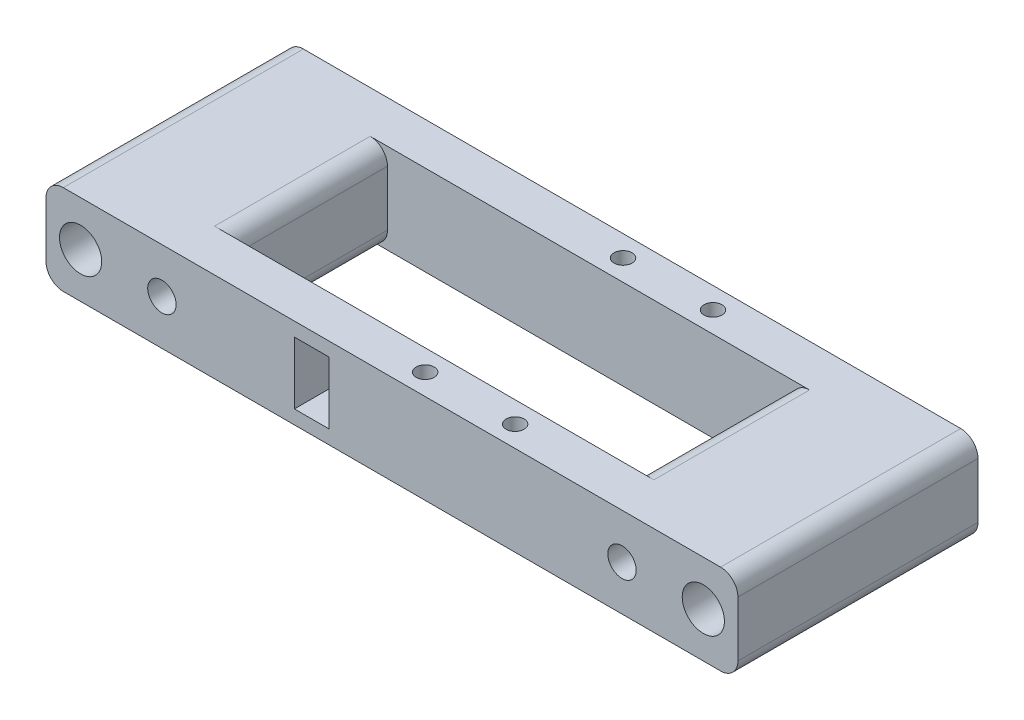
SolidWorks part; units mm, degrees
ref_plane "Front Plane" through (0, 0, 0) normal (0, 0, 1) x (1, 0, 0)
ref_plane "Top Plane" through (0, 0, 0) normal (0, 1, 0) x (1, 0, 0)
ref_plane "Right Plane" through (0, 0, 0) normal (1, 0, 0) x (0, 0, -1)
sketch "Sketch1" plane through (0, 0, 0) normal (0, 0, 1) x (1, 0, 0)
  line L0 (-58.5, 26) -> (-58.5, 0) construction
  line L1 (0, 0) -> (-100, 0)
  line L2 (0, 0) -> (0, 26)
  line L3 (0, 26) -> (-100, 26)
  line L4 (-100, 0) -> (-100, 26)
  circle A0 centre (-90, 13) radius 6.1
  circle A1 centre (-66.5, 13) radius 4.1
  point P9 (-100, 13)
  dimension "D3" = 12.2
  dimension "D4" = 8.2
  dimension "D1" = 100
  dimension "D2" = 26
  dimension "D5" = 23.5
  dimension "D6" = 10
  dimension "D7" = 8
  dimension "D8" = 41.5
extrude "Boss-Extrude1" add sketch "Sketch1" along normal blind 40
sketch "Sketch2" plane through (0, 0, 0) normal (0, 0, -1) x (-1, 0, 0)
  line L1 (100, 26) -> (0, 26)
  line L2 (100, 26) -> (100, 0)
  line L3 (100, 0) -> (0, 0)
  line L4 (0, 26) -> (0, 0)
extrude "Boss-Extrude2" add sketch "Sketch2" along normal blind 29.4
sketch "Sketch3" plane through (0, 26, 0) normal (0, 1, 0) x (1, 0, 0)
  line L0 (0, -40) -> (0, 29.4) construction
  line L1 (0, 17.2) -> (-58.5, 17.2)
  line L2 (0, 17.2) -> (0, -27.8)
  line L3 (0, -27.8) -> (-58.5, -27.8)
  line L4 (-58.5, 17.2) -> (-58.5, -27.8)
  line L5 (-100, -40) -> (-100, 29.4) construction
  line L6 (-100, 29.4) -> (0, 29.4) construction
  line L7 (0, -40) -> (-100, -40) construction
  dimension "D1" = 41.5
  dimension "D2" = 12.2
  dimension "D3" = 12.2
extrude "Cut-Extrude1" cut sketch "Sketch3" against normal up to next
mirror "Mirror2" about plane through (0, 0, 40) normal (-1, 0, 0) of "Boss-Extrude2", "Cut-Extrude1", "Boss-Extrude1"
sketch "Sketch4" plane through (0, 26, 0) normal (0, 1, 0) x (1, 0, 0)
  line L0 (-100, 29.4) -> (100, 29.4) construction
  line L1 (-5.5, 29.4) -> (-5.5, 17.2) construction
  line L2 (58.5, 17.2) -> (-58.5, 17.2) construction
  line L3 (58.5, 17.2) -> (58.5, -27.8) construction
  circle A0 centre (3.5, 23.3) radius 2.6
  circle A1 centre (29.5, 23.3) radius 2.6
  dimension "D1" = 6.1
  dimension "D3" = 9
  dimension "D4" = 26
  dimension "D5" = 5.2
  dimension "D2" = 64
extrude "Cut-Extrude2" cut sketch "Sketch4" against normal through all
sketch "Sketch5" plane through (0, 0, 0) normal (0, -1, 0) x (1, 0, 0)
  line L1 (34.2343, -23.3) -> (31.8671, -19.2)
  line L2 (31.8671, -19.2) -> (27.1329, -19.2)
  line L3 (27.1329, -19.2) -> (24.7657, -23.3)
  line L4 (24.7657, -23.3) -> (27.1329, -27.4)
  line L5 (27.1329, -27.4) -> (31.8671, -27.4)
  line L6 (31.8671, -27.4) -> (34.2343, -23.3)
  line L7 (-1.2343, -23.3) -> (1.1329, -27.4)
  line L8 (1.1329, -27.4) -> (5.8671, -27.4)
  line L9 (5.8671, -27.4) -> (8.2343, -23.3)
  line L10 (8.2343, -23.3) -> (5.8671, -19.2)
  line L11 (5.8671, -19.2) -> (1.1329, -19.2)
  line L12 (1.1329, -19.2) -> (-1.2343, -23.3)
  circle A0 centre (29.5, -23.3) radius 4.1 construction
  circle A1 centre (3.5, -23.3) radius 4.1 construction
  dimension "D1" = 8.2
  dimension "D2" = 8.2
extrude "Cut-Extrude3" cut sketch "Sketch5" against normal blind 4
ref_plane "Plane1" through (0, 0, 5.3) normal (0, 0, 1) x (1, 0, 0)
mirror "Mirror3" about plane through (0, 0, 5.3) normal (0, 0, 1) of "Cut-Extrude3", "Cut-Extrude2"
sketch "Sketch6" plane through (0, 0, 40) normal (0, 0, 1) x (1, 0, 0)
  line L0 (-8.1, 26) -> (-8.1, 0) construction
  line L1 (100, 26) -> (-100, 26) construction
  line L2 (-100, 0) -> (100, 0) construction
  line L3 (0.9, 26) -> (0.9, 4) construction
  line L4 (-100, 26) -> (-100, 0) construction
  line L5 (-18.2, 22) -> (-28.2, 22)
  line L6 (-18.2, 22) -> (-18.2, 4)
  line L7 (-18.2, 4) -> (-28.2, 4)
  line L8 (-28.2, 22) -> (-28.2, 4)
  point P12 (-28.2, 13)
  point P15 (-100, 13)
  dimension "D1" = 9
  dimension "D2" = 10.1
  dimension "D3" = 10
  dimension "D4" = 18
extrude "Cut-Extrude4" cut sketch "Sketch6" against normal up to vertex (12.2 mm away) up to point (-58.5, 26, 27.8)
fillet "Fillet1" radius 5 8 edges at (58.5, 0, 5.3) (-58.5, 0, 5.3) (58.5, 26, 5.3) (100, 0, 5.3) (100, 26, 5.3) (-100, 0, 5.3) (-100, 26, 5.3) (-58.5, 26, 5.3)
